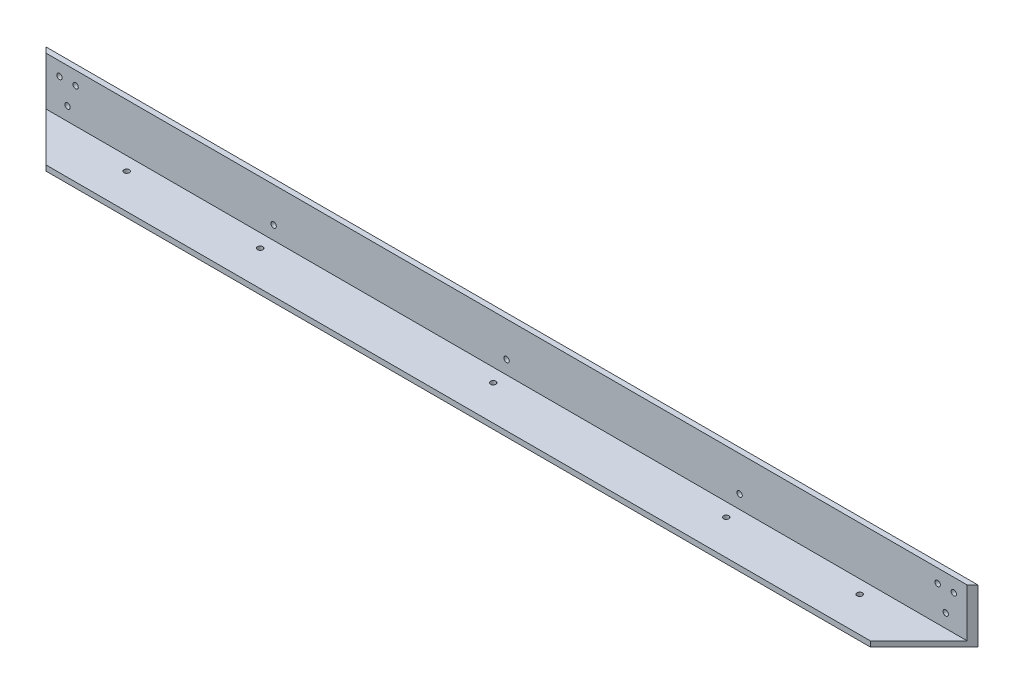
SolidWorks part; units mm, degrees
ref_plane "Front Plane" through (0, 0, 0) normal (0, 0, 1) x (1, 0, 0)
ref_plane "Top Plane" through (0, 0, 0) normal (0, 1, 0) x (1, 0, 0)
ref_plane "Right Plane" through (0, 0, 0) normal (1, 0, 0) x (0, 0, -1)
sketch "Sketch1" plane through (0, 0, 0) normal (1, 0, 0) x (0, 0, -1)
  line L0 (0, 0) -> (-31.75, 0)
  line L1 (-31.75, 0) -> (-31.75, 3.175)
  line L2 (-31.75, 3.175) -> (-3.175, 3.175)
  line L3 (-3.175, 3.175) -> (-3.175, 31.75)
  line L4 (-3.175, 31.75) -> (0, 31.75)
  line L5 (0, 31.75) -> (0, 0)
  dimension "LHeight" = 31.75
  dimension "LWidth" = 31.75
  dimension "LMaterialThickness" = 3.175
  dimension "D1" = 28.575
  dimension "D2" = 28.575
  dimension "D3" = 3.175
extrude "Boss-Extrude1" add sketch "Sketch1" along normal blind 550
chamfer "Chamfer6" distance 31.75 angle 45 1 edges at (550, 1.5875, 31.75)
chamfer "Chamfer7" distance 31.75 angle 45 1 edges at (0, 1.5875, 31.75)
sketch "TopHoles-Sketch3" plane through (0, 3.175, 0) normal (0, 1, 0) x (1, 0, 0)
  line L0 (550, 0) -> (0, 0) construction
  circle A9 centre (491.2625, -11.1125) radius 1.5875
  circle A10 centre (58.7375, -11.1125) radius 1.5875
  circle A13 centre (137.5, -11.1125) radius 1.5875
  circle A14 centre (275, -11.1125) radius 1.5875
  circle A15 centre (412.5, -11.1125) radius 1.5875
  dimension "D8" = 137.5
  dimension "D10" = 137.5
  dimension "D5" = 3.175
  dimension "D11" = 137.5
  dimension "D2" = 11.1125
  dimension "D3" = 58.7375
  dimension "D4" = 58.7375
extrude "TopHoles-Cut-Extrude2" cut sketch "TopHoles-Sketch3" against normal through all
sketch "RightHoles-Sketch4" plane through (0, 0, 3.175) normal (0, 0, 1) x (1, 0, 0)
  line L1 (550, 0) -> (0, 0) construction
  line L3 (550, 31.75) -> (0, 31.75) construction
  line L4 (0, 0) -> (0, 31.75) construction
  line L5 (550, 0) -> (550, 31.75) construction
  circle A1 centre (11.1125, 23.8125) radius 1.5875
  circle A3 centre (529.3625, 23.8125) radius 1.5875
  circle A4 centre (20.6375, 23.8125) radius 1.5875
  circle A5 centre (538.8875, 23.8125) radius 1.5875
  circle A7 centre (15.875, 11.1125) radius 1.5875
  circle A8 centre (534.125, 11.1125) radius 1.5875
  circle A10 centre (137.5, 11.1125) radius 1.5875
  circle A11 centre (275, 11.1125) radius 1.5875
  circle A12 centre (412.5, 11.1125) radius 1.5875
  dimension "D2" = 3.175
  dimension "D4" = 7.9375
  dimension "D1" = 11.1125
  dimension "D6" = 20.6375
  dimension "D3" = 11.1125
  dimension "D5" = 20.6375
  dimension "D8" = 137.5
  dimension "D9" = 137.5
  dimension "D10" = 137.5
  dimension "D7" = 11.1125
  dimension "D11" = 15.875
  dimension "D12" = 15.875
extrude "RightHoles-Cut-Extrude3" cut sketch "RightHoles-Sketch4" against normal through all
equation "\"TopRailWidth\"= 1.25in"
equation "\"TopRailHeight\"= 1.25in"
equation "\"RailThickness\"= .125in'Spec"
equation "\"SideRailHoleY1FromEdge\"= \"HoleOffsetFromEdge\""
equation "\"SideRailHoleX1FromSide\"= \"HoleOffsetFromSide\""
equation "\"SideRailLength\"= 550mm"
equation "\"VSWidth\"= 1.25in'Spec"
equation "\"HoleOffsetFromEdge\"= \"RailThickness\" * 2.5"
equation "\"HoleOffsetFromSide\"= \"RailThickness\" * 3.5"
equation "\"TopHoleY1FromSide\"= \"HoleOffsetFromSide\""
equation "\"SideRailHoleX2FromSide\"= \"VSWidth\" - \"HoleOffsetFromEdge\" - \"RailThickness\"'Equals 20.6375"
equation "\"FasteningHoleDiameter\"= .125in"
equation "\"SideRailHoleY2FromSide\"= \"HoleOffsetFromSide\""
equation "\"D2@RightHoles-Sketch4\"=\"FasteningHoleDiameter\""
equation "\"LWidth@Sketch1\"=\"TopRailWidth\""
equation "\"LHeight@Sketch1\"=\"TopRailHeight\""
equation "\"LMaterialThickness@Sketch1\"=\"RailThickness\""
equation "\"D1@Boss-Extrude1\"=\"SideRailLength\""
equation "\"D4@RightHoles-Sketch4\"=\"SideRailHoleY1FromEdge\""
equation "\"D1@Chamfer6\"=\"TopRailWidth\""
equation "\"D1@Chamfer7\"=\"TopRailWidth\""
equation "\"D1@RightHoles-Sketch4\"=\"SideRailHoleX1FromSide\""
equation "\"D6@RightHoles-Sketch4\"=\"SideRailHoleX2FromSide\""
equation "\"D3@RightHoles-Sketch4\"=\"SideRailHoleX1FromSide\""
equation "\"D5@RightHoles-Sketch4\"=\"SideRailHoleX2FromSide\""
equation "\"TopCBLength\"= \"TopRailWidth\" * 2'Equals 63.5"
equation "\"LeftOrRightEnclosureOffsets\"= \"SideRailLength\" / 4"
equation "\"D8@TopHoles-Sketch3\"=\"LeftOrRightEnclosureOffsets\""
equation "\"D10@TopHoles-Sketch3\"=\"LeftOrRightEnclosureOffsets\""
equation "\"D11@TopHoles-Sketch3\"=\"LeftOrRightEnclosureOffsets\""
equation "\"D8@RightHoles-Sketch4\"=\"LeftOrRightEnclosureOffsets\""
equation "\"D9@RightHoles-Sketch4\"=\"LeftOrRightEnclosureOffsets\""
equation "\"D10@RightHoles-Sketch4\"=\"LeftOrRightEnclosureOffsets\""
equation "\"D7@RightHoles-Sketch4\"=\"SideRailHoleY2FromSide\""
equation "\"LeftOrRightCornerEnclosureOffset\"= \"RailThickness\" + \"TopCBLength\" - \"HoleOffsetFromEdge\"'Equals 58.7375"
equation "\"D2@TopHoles-Sketch3\"=\"TopHoleY1FromSide\""
equation "\"D3@TopHoles-Sketch3\"=\"LeftOrRightCornerEnclosureOffset\""
equation "\"D4@TopHoles-Sketch3\"=\"LeftOrRightCornerEnclosureOffset\""
equation "\"D5@TopHoles-Sketch3\"=\"FasteningHoleDiameter\""
equation "\"VSMidSideRailHoleXFromSideToCenter\"= \"RailThickness\" * 6"
equation "\"D11@RightHoles-Sketch4\"=\"VSMidSideRailHoleXFromSideToCenter\" - \"RailThickness\""
equation "\"D12@RightHoles-Sketch4\"=\"VSMidSideRailHoleXFromSideToCenter\" - \"RailThickness\""
